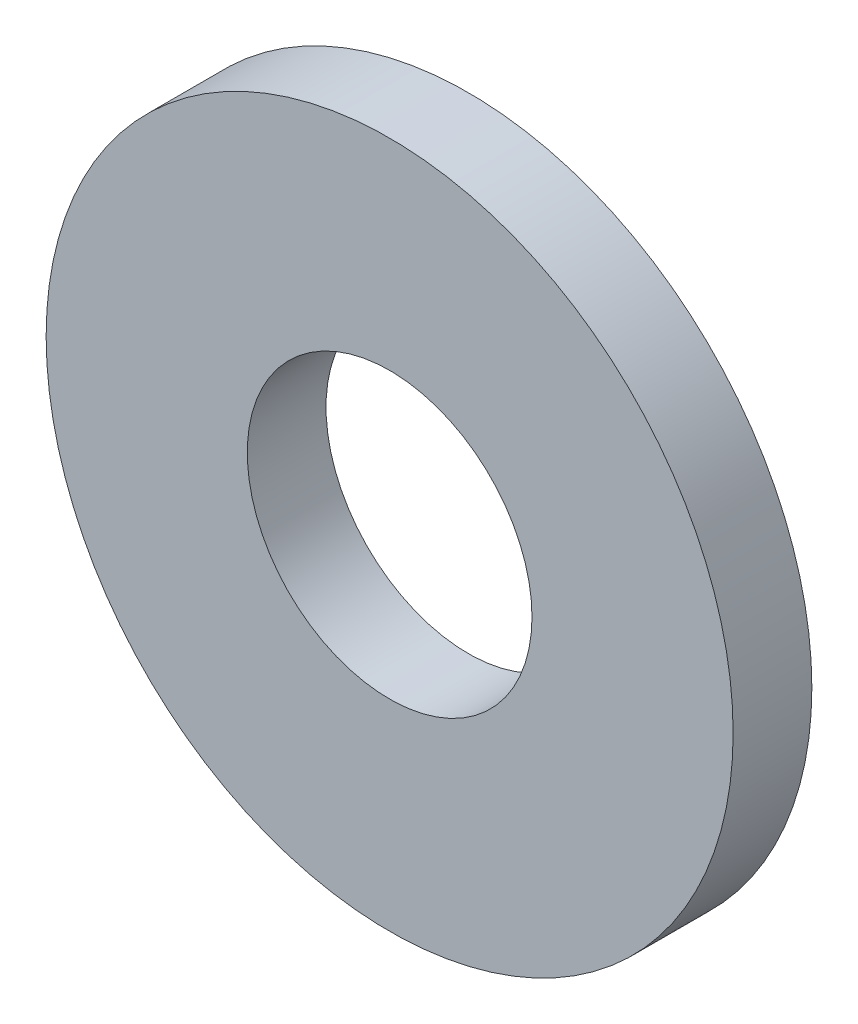
SolidWorks part; units mm, degrees
ref_plane "Front Plane" through (0, 0, 0) normal (0, 0, 1) x (1, 0, 0)
ref_plane "Top Plane" through (0, 0, 0) normal (0, 1, 0) x (1, 0, 0)
ref_plane "Right Plane" through (0, 0, 0) normal (1, 0, 0) x (0, 0, -1)
sketch "Sketch1" plane through (0, 0, 0) normal (0, 0, 1) x (1, 0, 0)
  circle A0 centre (0, 0) radius 43.6326
extrude "Boss-Extrude1" add sketch "Sketch1" along normal blind 10
sketch "Sketch2" plane through (0, 0, 10) normal (0, 0, 1) x (1, 0, 0)
  circle A0 centre (0, 0) radius 18.0827
extrude "Cut-Extrude1" cut sketch "Sketch2" against normal up to surface (10 mm away) up to face at (43.6326, 0, 0)
